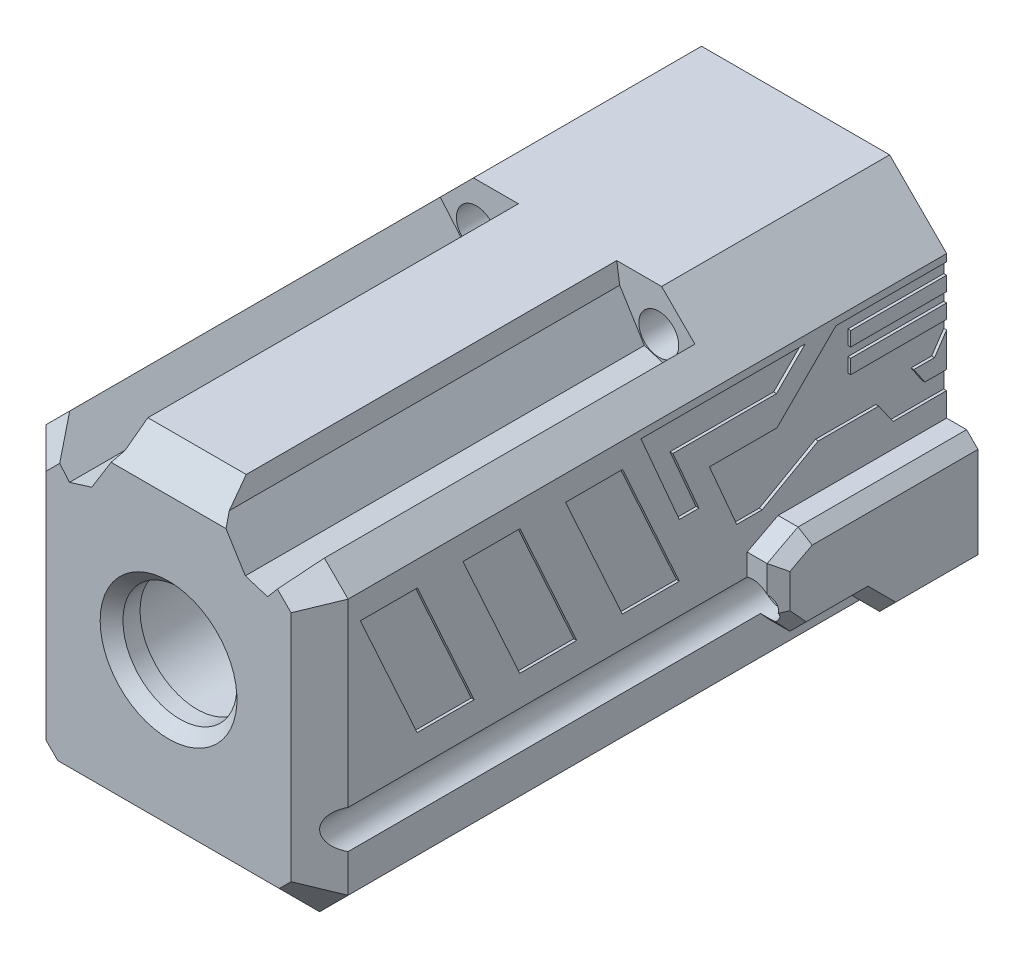
SolidWorks part; units mm, degrees
ref_plane "정면" through (0, 0, 0) normal (0, 0, 1) x (1, 0, 0)
ref_plane "윗면" through (0, 0, 0) normal (0, 1, 0) x (1, 0, 0)
ref_plane "우측면" through (0, 0, 0) normal (1, 0, 0) x (0, 0, -1)
sketch "스케치1" plane through (0, 0, 0) normal (1, 0, 0) x (0, 0, -1)
  line L0 (0, 0) -> (0, -55)
  line L1 (0, -55) -> (-24.0271, -55)
  line L2 (-110, -60) -> (-110, 0)
  line L3 (-110, 0) -> (0, 0)
  line L4 (-24.0271, -55) -> (-26.3656, -60)
  line L5 (-26.3656, -60) -> (-110, -60)
  dimension "D1" = 55
  dimension "D2" = 110
  dimension "D3" = 60
extrude "보스-돌출1" add sketch "스케치1" along normal mid plane 53
sketch "스케치2" plane through (0, 0, 0) normal (0, 0, 1) x (1, 0, 0)
  line L0 (0, 0) -> (0, -30) construction
  line L1 (22.575, -30) -> (22.575, -55)
  line L2 (26.5, -55) -> (-26.5, -55) construction
  line L3 (22.575, -55) -> (-22.575, -55)
  line L4 (-22.575, -55) -> (-22.575, -30)
  arc A0 (22.575, -30) -> (-22.575, -30) centre (0, -30) ccw
  dimension "D1" = 45.15
  dimension "D2" = 30
extrude "컷-돌출1" cut sketch "스케치2" along normal blind 20
sketch "스케치3" plane through (0, 0, 110) normal (0, 0, 1) x (1, 0, 0)
  circle A0 centre (0, -30) radius 10
  dimension "D1" = 20
sketch "스케치6" plane through (0, 0, 0) normal (1, 0, 0) x (0, 0, -1)
  line L0 (-20, -46.1122) -> (-23.1998, -55)
  line L1 (-20, -30) -> (-20, -55) construction
  line L2 (-24.0271, -55) -> (0, -55) construction
  line L3 (-23.1998, -55) -> (-20, -55)
  line L4 (-20, -55) -> (-20, -46.1122)
extrude "컷-돌출4" cut sketch "스케치6" against normal mid plane 45.2
sketch "스케치7" plane through (0, 0, 0) normal (1, 0, 0) x (0, 0, -1)
  line L0 (-20, -30) -> (-20, -46.1122) construction
  line L1 (-20, -46.5) -> (-10.7, -46.5)
  line L2 (-20, -46.5) -> (-20, -40)
  line L3 (-20, -40) -> (-10.7, -40)
  line L4 (-10.7, -46.5) -> (-10.7, -40)
  dimension "D1" = 9.3
  dimension "D2" = 6.5
  dimension "D3" = 40
extrude "보스-돌출2" add sketch "스케치7" along normal mid plane 46
chamfer "모따기1" distance 2.5 angle 45 2 edges at (0, -46.5, 10.7) (0, -40, 10.7)
chamfer "모따기2" distance 10 angle 45 2 edges at (-26.5, 0, 55) (26.5, 0, 55)
sketch "스케치8" plane through (0, 1.0832, 3.0088) normal (0, -0.3387, -0.9409) x (-1, 0, 0)
  line L0 (0, 0) -> (0, -102.7837) construction
  line L1 (-16.5, 0) -> (16.5, 0) construction
  circle A0 centre (-17, -55.4) radius 3.025
  circle A1 centre (17, -55.4) radius 3.025
  dimension "D1" = 6.05
  dimension "D2" = 17
  dimension "D3" = 55.4
extrude "컷-돌출5" cut sketch "스케치8" against normal blind 6
chamfer "모따기3" distance 5 angle 45 2 edges at (26.5, -60, 68.1828) (-26.5, -60, 68.1828)
sketch "스케치9" plane through (0, 0, 0) normal (1, 0, 0) x (0, 0, -1)
  line L0 (-10.7, -7.425) -> (-10.7, -9.425)
  line L1 (0, -7.425) -> (-20, -7.425) construction
  line L2 (-20, -30) -> (-20, -7.425) construction
  line L3 (-20, -18.425) -> (-20, -7.425)
  line L4 (-20, -7.425) -> (-10.7, -7.425)
  line L6 (-10.7, -9.425) -> (-10.7, -18.425)
  line L7 (-10.7, -18.425) -> (-20, -18.425)
  dimension "D1" = 2
  dimension "D2" = 9.3
  dimension "D3" = 11
extrude "보스-돌출3" add sketch "스케치9" along normal mid plane 40
sketch "스케치10" plane through (0, 0, 20) normal (0, 0, -1) x (-1, 0, 0)
  circle A0 centre (0, -30) radius 11.1
  dimension "D1" = 22.2
extrude "컷-돌출6" cut sketch "스케치10" against normal mid plane 170
extrude "컷-돌출7" cut sketch "스케치3" against normal through all
chamfer "모따기4" distance 2 angle 45 1 edges at (10, -30, 110)
sketch "스케치11" plane through (-26.5, 0, 0) normal (-1, 0, 0) x (0, 0, 1)
  line L0 (0, -55) -> (15.2556, -55)
  line L1 (24.0271, -55) -> (0, -55) construction
  line L2 (15.2556, -55) -> (20.1299, -50.1257)
  line L3 (20.1299, -50.1257) -> (31.0146, -50.1257)
  line L4 (31.0146, -50.1257) -> (35, -45.7901)
  line L5 (35, -45.7901) -> (35, -37.8432)
  line L6 (35, -37.8432) -> (29.5743, -35)
  line L7 (29.5743, -35) -> (0, -35)
  line L8 (0, -55) -> (0, -10) construction
  line L9 (0, -35) -> (0, -55)
  dimension "D1" = 20
  dimension "D2" = 35
extrude "보스-돌출4" add sketch "스케치11" along normal blind 5.5
chamfer "모따기5" distance 2 angle 45 7 edges at (-32, -55, 7.6278) (-32, -52.5628, 17.6927) (-32, -50.1257, 25.5723) (-32, -47.9579, 33.0073) (-32, -41.8167, 35) (-32, -36.4216, 32.2871) (-32, -35, 14.7871)
mirror "대칭 복사1" about plane through (0, 0, 0) normal (1, 0, 0) of "모따기5", "보스-돌출4"
sketch "스케치14" plane through (0, 0, 110) normal (0, 0, 1) x (1, 0, 0)
  line L0 (0, 0) -> (0, -78.1707) construction
  circle A0 centre (-27.5, -45) radius 1.95
  circle A1 centre (-16, -7.5) radius 1.95
  circle A2 centre (27.5, -45) radius 1.95
  circle A3 centre (16, -7.5) radius 1.95
  dimension "D1" = 3.9
  dimension "D2" = 3.9
  dimension "D3" = 16
  dimension "D4" = 27.5
  dimension "D5" = 45
  dimension "D6" = 7.5
extrude "컷-돌출8" cut sketch "스케치14" against normal through all
sketch "스케치15" plane through (0, 0, 110) normal (0, 0, 1) x (1, 0, 0)
  circle A0 centre (-16, -7.5) radius 3.5
  circle A1 centre (16, -7.5) radius 3.5
  circle A2 centre (-27.5, -45) radius 3.5
  circle A3 centre (27.5, -45) radius 3.5
  dimension "D1" = 7
  dimension "D2" = 7
  dimension "D3" = 7
  dimension "D4" = 7
extrude "컷-돌출9" cut sketch "스케치15" against normal blind 80
chamfer "모따기6" distance 5 angle 45 10 edges at (-26.5, -51.6771, 110) (-24, -57.5, 110) (0, -60, 110) (24, -57.5, 110) (26.5, -51.6771, 110) (26.5, -25.8229, 110) (21.5, -5, 110) (0, 0, 110) (-21.5, -5, 110) (-26.5, -25.8229, 110)
sketch "스케치16" plane through (0, 0, 110) normal (0, 0, 1) x (1, 0, 0)
  line L0 (-9.1449, -3.4908) -> (-13.4654, -10.4787)
  line L1 (-13.4654, -10.4787) -> (-17.3774, -11.699)
  line L2 (-25.4886, -2.1164) -> (-25.4886, 1.0626)
  line L3 (-25.4886, 1.0626) -> (-8.4705, 1.0626)
  line L4 (0, 0) -> (0, -63.5873) construction
  line L5 (-16.5, 0) -> (16.5, 0) construction
  line L6 (25.4886, 1.0626) -> (8.4705, 1.0626)
  line L7 (25.4886, -2.1164) -> (25.4886, 1.0626)
  line L8 (-9.1449, -3.4908) -> (-8.4705, 1.0626)
  line L9 (9.1449, -3.4908) -> (13.4654, -10.4787)
  line L10 (-17.3774, -11.699) -> (-25.4886, -2.1164)
  line L11 (13.4654, -10.4787) -> (17.3774, -11.699)
  line L12 (17.3774, -11.699) -> (25.4886, -2.1164)
  line L13 (9.1449, -3.4908) -> (8.4705, 1.0626)
extrude "컷-돌출10" cut sketch "스케치16" against normal blind 70
sketch "스케치17" plane through (0, -60, 0) normal (0, -1, 0) x (1, 0, 0)
  line L0 (0, 85) -> (0, 40) construction
  line L1 (0, 40) -> (0, 0) construction
  circle A0 centre (0, 40) radius 1.925
  circle A1 centre (0, 85) radius 1.925
  dimension "D1" = 3.85
  dimension "D2" = 3.85
  dimension "D3" = 40
  dimension "D4" = 45
extrude "컷-돌출11" cut sketch "스케치17" against normal up to next
sketch "스케치18" plane through (0, -60, 0) normal (0, -1, 0) x (1, 0, 0)
  circle A0 centre (0, 40) radius 3.5
  circle A1 centre (0, 85) radius 3.5
  dimension "D1" = 7
  dimension "D2" = 7
extrude "컷-돌출12" cut sketch "스케치18" against normal blind 4
sketch "스케치19" plane through (-26.5, 0, 0) normal (-1, 0, 0) x (0, 0, 1)
  line L0 (0, -11.2531) -> (19.423, -11.2531)
  line L1 (0, -35) -> (0, -10) construction
  line L2 (19.423, -11.2531) -> (29.7663, -21.5963)
  line L3 (29.7663, -21.5963) -> (41.6203, -21.5963)
  line L4 (41.6203, -21.5963) -> (36.8167, -32.7432)
  line L5 (36.8167, -32.7432) -> (32.3706, -32.7432)
  line L6 (32.3706, -32.7432) -> (22.5377, -27.213)
  line L7 (22.5377, -27.213) -> (11.9208, -27.213)
  line L8 (11.9208, -27.213) -> (9.406, -30.8147)
  line L9 (9.406, -30.8147) -> (0, -30.8147)
  line L10 (0, -30.8147) -> (0, -27.6087)
  line L11 (56.8527, -14.3678) -> (46.8911, -36.3281)
  line L12 (46.8911, -36.3281) -> (56.8911, -36.3281)
  line L13 (56.8911, -36.3281) -> (66.8527, -14.3678)
  line L14 (66.8527, -14.3678) -> (56.8527, -14.3678)
  line L15 (74.8527, -14.3678) -> (64.8911, -36.3281)
  line L16 (64.8911, -36.3281) -> (74.8911, -36.3281)
  line L17 (74.8911, -36.3281) -> (84.8527, -14.3678)
  line L18 (84.8527, -14.3678) -> (74.8527, -14.3678)
  line L19 (92.8527, -14.3678) -> (82.8911, -36.3281)
  line L20 (82.8911, -36.3281) -> (92.8911, -36.3281)
  line L21 (92.8911, -36.3281) -> (102.8527, -14.3678)
  line L22 (102.8527, -14.3678) -> (92.8527, -14.3678)
  line L23 (24.8153, -11.3268) -> (29.8404, -16.3519)
  line L24 (29.8404, -16.3519) -> (48.0287, -16.3519)
  line L25 (48.0287, -16.3519) -> (43.4589, -26.9538)
  line L26 (43.4589, -26.9538) -> (46.8965, -26.9538)
  line L27 (46.8965, -26.9538) -> (53.6322, -11.3268)
  line L28 (53.6322, -11.3268) -> (24.8153, -11.3268)
  line L29 (0, -21.5963) -> (2.1198, -24.7454)
  line L30 (0, -13.2846) -> (16.8325, -13.2846)
  line L31 (0, -13.2846) -> (0, -11.2531)
  line L32 (0, -15.7846) -> (16.8325, -15.7846)
  line L33 (16.8325, -13.2846) -> (16.8325, -15.7846)
  line L34 (0, -17.4969) -> (16.8325, -17.4969)
  line L35 (0, -17.4969) -> (0, -15.7846)
  line L36 (0, -19.9969) -> (16.8325, -19.9969)
  line L37 (16.8325, -17.4969) -> (16.8325, -19.9969)
  line L38 (2.1198, -24.7454) -> (5.7567, -24.7454)
  line L39 (5.7567, -24.7454) -> (3.812, -27.6087)
  line L40 (3.812, -27.6087) -> (0, -27.6087)
  line L41 (0, -21.5963) -> (0, -19.9969)
  dimension "D1" = 10
  dimension "D2" = 10
  dimension "D3" = 10
  dimension "D4" = 8
  dimension "D5" = 8
  dimension "D6" = 2.5
  dimension "D7" = 2.5
extrude "컷-돌출13" cut sketch "스케치19" against normal blind 0.5
mirror "대칭 복사2" about plane through (0, 0, 0) normal (1, 0, 0) of "컷-돌출13"
chamfer "모따기7" distance 0.3 angle 45 1 edges at (0, -18.425, 10.7)
